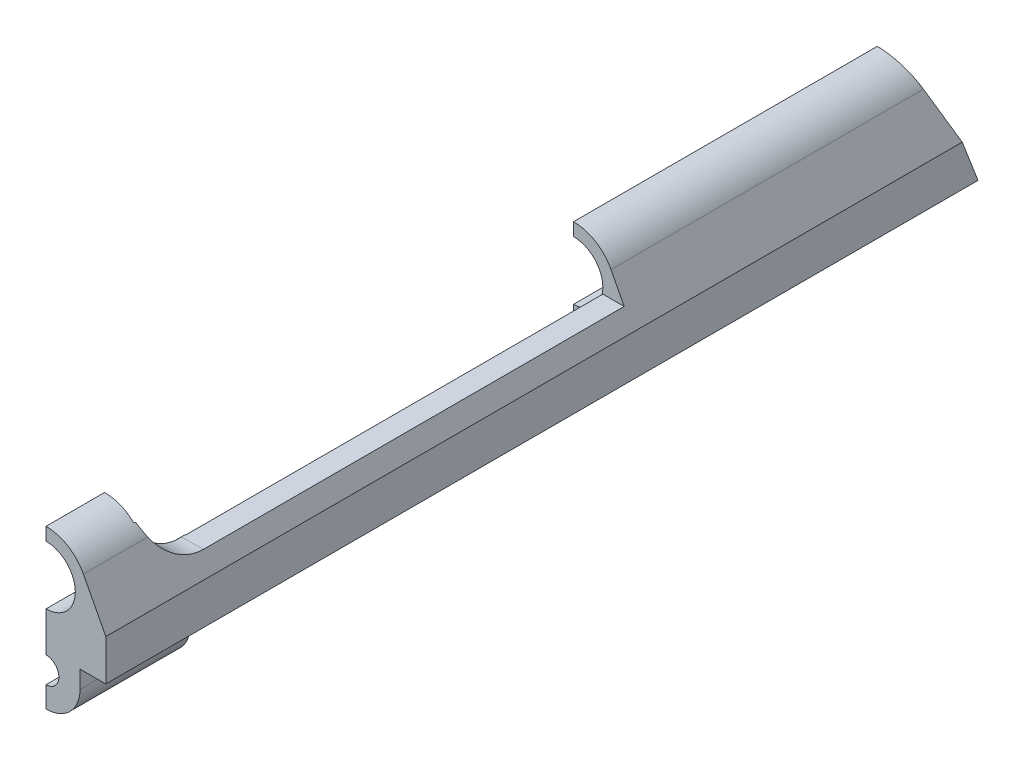
SolidWorks part; units mm, degrees
ref_plane "Front Plane" through (0, 0, 0) normal (0, 0, 1) x (1, 0, 0)
ref_plane "Top Plane" through (0, 0, 0) normal (0, 1, 0) x (1, 0, 0)
ref_plane "Right Plane" through (0, 0, 0) normal (1, 0, 0) x (0, 0, -1)
sketch "Sketch1" plane through (0, 0, 0) normal (1, 0, 0) x (0, 0, -1)
  line L1 (0, 0) -> (188.976, 0)
  line L2 (0, 0) -> (0, 34.29)
  line L3 (0, 34.29) -> (188.976, 34.29)
  line L4 (188.976, 0) -> (188.976, 34.29)
  dimension "D1" = 188.976
  dimension "D2" = 34.29
extrude "Boss-Extrude1" add sketch "Sketch1" along normal blind 12.954
sketch "Sketch2" plane through (0, 0, 0) normal (0, 0, 1) x (1, 0, 0)
  line L0 (0, 34.29) -> (0, 0) construction
  circle A0 centre (0, 7.366) radius 2.794
  circle A1 centre (0, 25.146) radius 6.35
  line M1 (0, 34.29) -> (0, 0)
  dimension "D1" = 12.7
  dimension "D2" = 5.588
  dimension "D3" = 17.78
  dimension "D4" = 7.366
extrude "Cut-Extrude1" cut sketch "Sketch2" against normal blind 121.412 contours A1 M1 region at (2.695, 25.146, 0)
extrude "Cut-Extrude2" cut sketch "Sketch2<3>" against normal blind 25.4 contours A0 M1 region at (1.1858, 7.366, 0)
sketch "Sketch2<3>" plane through (0, 0, 0) normal (0, 0, 1) x (1, 0, 0) same geometry as "Sketch2"
sketch "Sketch3" plane through (0, 0, 0) normal (-1, 0, 0) x (0, 0, 1)
  line L1 (-188.976, 0) -> (-23.876, 0)
  line L2 (-188.976, 0) -> (-188.976, 11.176)
  line L3 (-188.976, 11.176) -> (-23.876, 11.176)
  line L4 (-23.876, 0) -> (-23.876, 11.176)
  dimension "D1" = 11.176
  dimension "D2" = 165.1
extrude "Cut-Extrude3" cut sketch "Sketch3" against normal through all
sketch "Sketch4" plane through (0, 0, 0) normal (0, 0, 1) x (1, 0, 0)
  line L0 (7.366, 7.366) -> (7.366, 11.176)
  line L1 (7.366, 11.176) -> (12.954, 11.176)
  line L2 (12.954, 11.176) -> (12.954, 0)
  line L3 (12.954, 0) -> (0, 0)
  circle A0 centre (0, 7.366) radius 7.366
  arc A1 (0, 4.572) -> (0, 10.16) centre (0, 7.366) ccw construction
  line M6 (0, 0) -> (12.954, 0)
  line M7 (12.954, 0) -> (12.954, 34.29)
  dimension "D1" = 3.81
extrude "Cut-Extrude4" cut sketch "Sketch4" against normal blind 25.4 contours A0 L1 L0 M6 M7 region at (9.4624, 4.9684, 0)
sketch "Sketch5" plane through (0, 34.29, 0) normal (0, 1, 0) x (1, 0, 0)
  line L0 (0, 188.976) -> (0, 0) construction
  line L1 (0, 12.7) -> (6.35, 12.7)
  line L2 (0, 12.7) -> (0, 114.3)
  line L3 (0, 114.3) -> (6.35, 114.3)
  line L4 (6.35, 12.7) -> (6.35, 114.3)
  line L6 (6.35, 12.7) -> (0, 12.7)
  line L7 (6.35, 12.7) -> (6.35, 23.876)
  line L8 (6.35, 23.876) -> (0, 23.876)
  line L9 (0, 12.7) -> (0, 23.876)
  line M5 (0, 188.976) -> (0, 0)
  dimension "D1" = 101.6
  dimension "D2" = 12.7
  dimension "D3" = 6.35
  dimension "D4" = 11.176
extrude "Cut-Extrude6" cut sketch "Sketch5" against normal through all contours L8 L4 L3 M5 region at (3.175, 34.29, -69.088)
extrude "Cut-Extrude7" cut sketch "Sketch5<4>" against normal blind 10.414 contours L4 L8 L2 L1 region at (3.175, 34.29, -18.288)
sketch "Sketch5<4>" plane through (0, 34.29, 0) normal (0, 1, 0) x (1, 0, 0) same geometry as "Sketch5"
sketch "Sketch6" plane through (0, 0, 0) normal (0, 0, 1) x (1, 0, 0)
  line L3 (8.1106, 29.3687) -> (12.954, 20.066)
  line L4 (12.954, 34.29) -> (12.954, 11.176) construction
  line L5 (0, 31.496) -> (0, 18.796) construction
  circle A0 centre (0, 25.146) radius 9.144
  point P16 (0, 25.146)
  line M7 (12.954, 11.176) -> (12.954, 34.29)
  line M8 (12.954, 34.29) -> (0, 34.29)
  dimension "D2" = 8.89
extrude "Cut-Extrude8" cut sketch "Sketch6" against normal through all contours A0 L3 M7 M8 region at (9.9912, 29.8776, 0)
sketch "Sketch7" plane through (6.35, 0, 0) normal (-1, 0, 0) x (0, 0, 1)
  line L0 (0, 29.3687) -> (0, 20.066) construction
  line L1 (-114.3, 34.29) -> (-12.7, 34.29)
  line L2 (-114.3, 34.29) -> (-114.3, 23.876)
  line L3 (-114.3, 23.876) -> (-12.7, 23.876)
  line L4 (-12.7, 34.29) -> (-12.7, 23.876)
  circle A0 centre (-23.114, 34.29) radius 10.414
  line M5 (-12.7, 31.7255) -> (-114.3, 31.7255)
  line M6 (-114.3, 31.7255) -> (-114.3, 25.146)
  line M7 (-114.3, 25.146) -> (-114.3, 11.176)
  line M10 (-23.876, 23.876) -> (-12.7, 23.876)
extrude "Cut-Extrude9" cut sketch "Sketch7" against normal through all contours A0 L3 M5 M6 M7 M10 | A0 L1 L2 M5 | A0 M5 | L1 A0 M5 region at (6.35, 33.0069, -73.8608) region at (6.35, 33.0144, -23.114) region at (6.35, 27.7422, -72.4178) region at (6.35, 28.4553, -23.114)
sketch "Sketch8" plane through (0, 0, 0) normal (-1, 0, 0) x (0, 0, 1)
  line L0 (-188.976, 11.176) -> (-180.1034, 34.29)
  line L1 (-188.976, 34.29) -> (-114.3, 34.29) construction
  line L2 (-114.3, 11.176) -> (-188.976, 11.176) construction
  line M8 (-114.3, 34.29) -> (-188.976, 34.29)
  line M9 (-188.976, 34.29) -> (-188.976, 11.176)
  dimension "D1" = 69
extrude "Cut-Extrude10" cut sketch "Sketch8" against normal through all and the other way through all contours L0 M9 M8 region at (0, 26.5853, -186.0185)
sketch3d "3DSketch1"
  line L0 (12.954, 11.176, -188.976) -> (0, 11.176, -188.976) construction
sketch "Sketch12" plane through (0, 0, -188.976) normal (0, 0, 1) x (1, 0, 0)
  line L1 (12.954, 11.176) -> (12.954, 13.97)
  line L14 (12.954, 11.176) -> (8.382, 11.176)
  line L15 (12.954, 11.176) -> (12.954, 13.97)
  line L16 (12.954, 13.97) -> (8.382, 13.97)
  line L17 (8.382, 11.176) -> (8.382, 13.97)
  line L18 (8.382, 13.97) -> (10.922, 13.97)
  line L19 (8.382, 13.97) -> (8.382, 18.542)
  line L20 (8.382, 18.542) -> (10.922, 18.542)
  line L21 (10.922, 13.97) -> (10.922, 18.542)
  line L22 (8.382, 18.542) -> (0, 18.542)
  line L23 (8.382, 18.542) -> (8.382, 11.176)
  line L24 (8.382, 11.176) -> (0, 11.176)
  line L25 (0, 18.542) -> (0, 11.176)
  dimension "D1" = 4.572
  dimension "D2" = 2.794
  dimension "D3" = 2.54
  dimension "D6" = 4.572
extrude "Cut-Extrude12" cut sketch "Sketch12" along normal blind 67.31 contours L22 L25 L24 L17 L19 | L16 L21 L20 L19 region at (4.191, 14.859, -188.976) region at (9.652, 16.256, -188.976)
